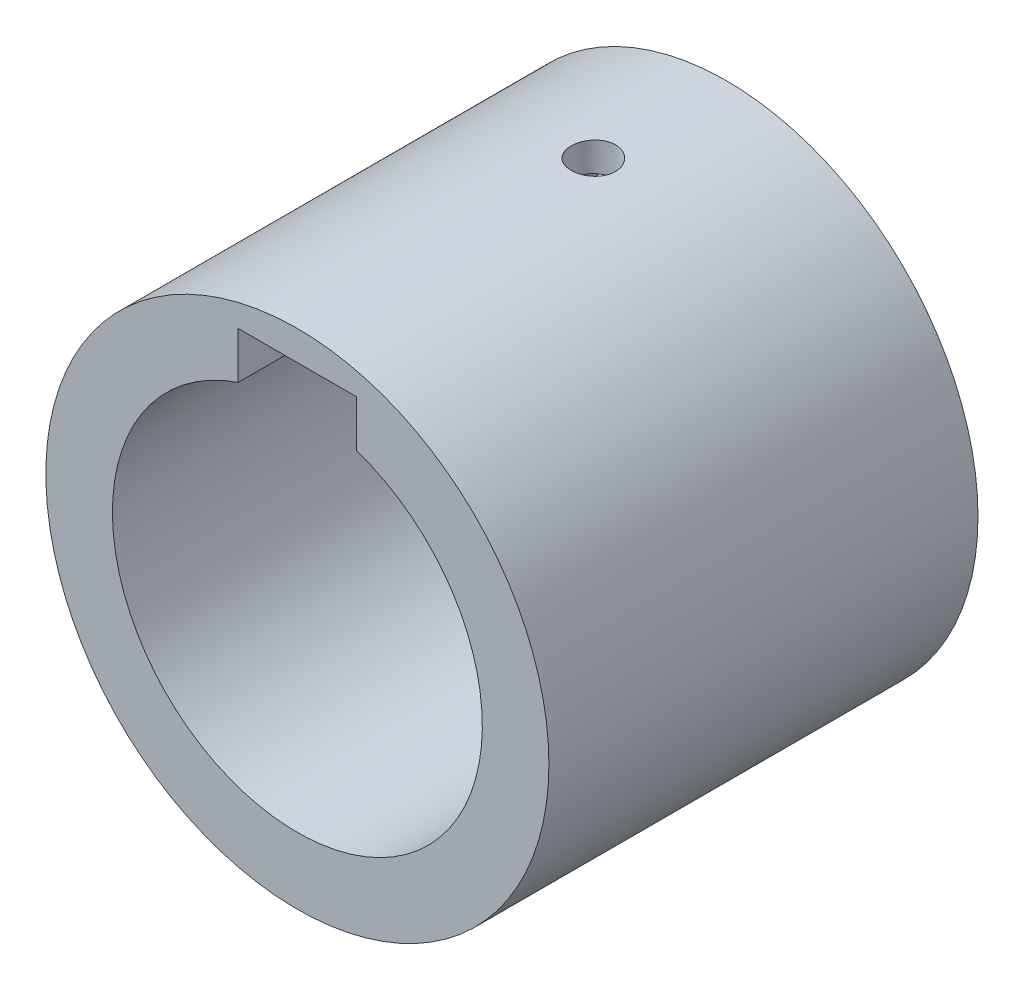
SolidWorks part; units mm, degrees
ref_plane "Front Plane" through (0, 0, 0) normal (0, 0, 1) x (1, 0, 0)
ref_plane "Top Plane" through (0, 0, 0) normal (0, 1, 0) x (1, 0, 0)
ref_plane "Right Plane" through (0, 0, 0) normal (1, 0, 0) x (0, 0, -1)
sketch "Sketch1" plane through (0, 0, 0) normal (0, 0, 1) x (1, 0, 0)
  circle A0 centre (0, 0) radius 12.5
  circle A1 centre (0, 0) radius 17
  dimension "D1" = 34
  dimension "D2" = 25
extrude "Boss-Extrude1" add sketch "Sketch1" along normal blind 29
sketch "Sketch2" plane through (0, 0, 29) normal (0, 0, 1) x (1, 0, 0)
  line L1 (-4, 15) -> (4, 15)
  line L2 (-4, 15) -> (-4, 10)
  line L3 (-4, 10) -> (4, 10)
  line L4 (4, 15) -> (4, 10)
  line L5 (-4, 15) -> (4, 10) construction
  line L6 (-4, 10) -> (4, 15) construction
  circle A0 centre (0, 0) radius 12.5 construction
  point P0 (0, 12.5)
  dimension "D1" = 5
  dimension "D2" = 8
  dimension "D3" = 2.5
extrude "Cut-Extrude2" cut sketch "Sketch2" against normal blind 28
fillet "Fillet3" radius 4 1 edges at (-4, 13.4214, 1)
fillet "Fillet4" radius 4 1 edges at (4, 13.4214, 1)
sketch "Sketch3" plane through (0, 15, 0) normal (0, -1, 0) x (-1, 0, 0)
  line L0 (0, -1) -> (0, -29) construction
  line L1 (-4, -29) -> (4, -29) construction
  circle A0 centre (0, -9) radius 1.5
  dimension "D1" = 8
  dimension "D2" = 3
extrude "Cut-Extrude4" cut sketch "Sketch3" against normal through all
